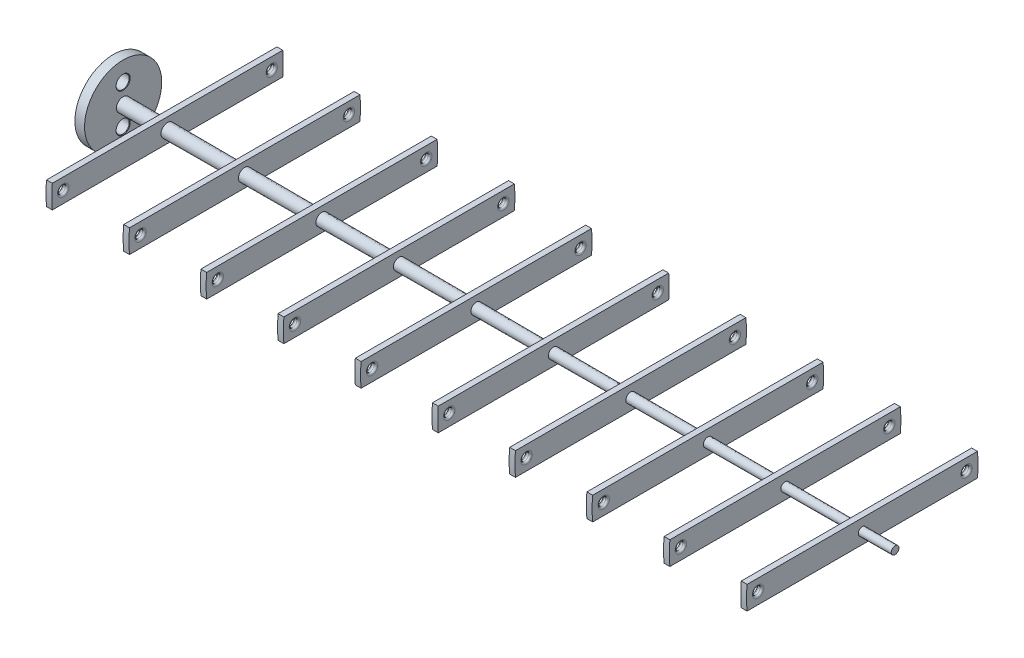
SolidWorks part; units mm, degrees
ref_plane "Front Plane" through (0, 0, 0) normal (0, 0, 1) x (1, 0, 0)
ref_plane "Top Plane" through (0, 0, 0) normal (0, 1, 0) x (1, 0, 0)
ref_plane "Right Plane" through (0, 0, 0) normal (1, 0, 0) x (0, 0, -1)
sketch "Sketch2" plane through (0, 0, 0) normal (0, 0, 1) x (1, 0, 0)
  line L0 (0, 1.75) -> (200, 1)
  line L1 (0, -11) -> (0, 11) construction
  line L2 (200, 1) -> (200, 0)
  line L3 (200, 0) -> (0, 0)
  line L4 (0, 0) -> (0, 1.75)
  dimension "D1" = 1.75
  dimension "D2" = 200
  dimension "D3" = 1
revolve "Revolve1" add sketch "Sketch2" angle 360 about L3
ref_axis "Axis1" through (-3.9062, 0, 0) along (1, 0, 0)
sketch "Sketch3" plane through (0, 0, 0) normal (0, 0, 1) x (1, 0, 0)
  line L0 (10, 0) -> (10, 30)
  line L1 (10, 30) -> (11.5, 30)
  line L2 (11.5, 30) -> (11.5, 0)
  line L3 (11.5, 0) -> (10, 0)
  line L4 (0, -24.75) -> (0, 24.75) construction
  dimension "D1" = 1.5
  dimension "D2" = 30
  dimension "D3" = 10
revolve "Revolve2" add sketch "Sketch3" angle 360 about L3
sketch "Sketch5" plane through (11.5, 0, 0) normal (1, 0, 0) x (0, 0, -1)
  line L0 (-27, 0) -> (0, 0) construction
  line L1 (0, 0) -> (27, 0) construction
  circle A0 centre (-27, 0) radius 1
  circle A1 centre (27, 0) radius 1
  dimension "D2" = 2
  dimension "D1" = 27
extrude "Cut-Extrude1" cut sketch "Sketch5" against normal up to next
fillet "Fillet1" radius 0.5 4 edges at (10, -1, -27) (10, -1, 27) (11.5, 1, 27) (11.5, 1, -27)
sketch "Sketch24" plane through (11.5, 0, 0) normal (1, 0, 0) x (0, 0, -1)
  line L0 (-29.8492, 3.0039) -> (29.8492, 3.0039)
  line L1 (-29.8496, -3) -> (29.8496, -3)
  circle A0 centre (0, 0) radius 30 construction
  arc A1 (-29.8496, -3) -> (29.8496, -3) centre (0, 0) ccw
  circle M6 centre (0, 0) radius 30
  dimension "D1" = 3.0039
  dimension "D2" = 3
extrude "Cut-Extrude2" cut sketch "Sketch24" against normal through all and the other way through all contours L0 M6 | L1 M6 region at (11.5, 14.3704, 0) region at (11.5, -14.3683, 0)
pattern_linear "LPattern1" count 10 spacing 20 along (1, 0, 0) of "Revolve2", "Cut-Extrude2", "Cut-Extrude1", "Fillet1"
sketch "Sketch16" plane through (0, 0, 0) normal (-1, 0, 0) x (0, 0, 1)
  circle A0 centre (0, 0) radius 10
  dimension "D1" = 20
extrude "Boss-Extrude1" add sketch "Sketch16" along normal blind 2.5
sketch "Sketch19" plane through (0, 0, 0) normal (-1, 0, 0) x (0, 0, 1)
  line L0 (0, 5) -> (0, -5) construction
  line L1 (0, -3.3021) -> (0, 3.3021) construction
  point P7 (0, 0)
  point P9 (0, 5)
  point P11 (0, -5)
  dimension "D1" = 10
sketch "Sketch22" plane through (0, 0, 0) normal (1, 0, 0) x (0, 0, -1)
  point P9 (0, 5)
  point P12 (0, -5)
hole_wizard "M3 Clearance Hole2" positions "Sketch22" profile "Sketch21" hole size "M3" standard "ANSI Metric" end condition up to next
sketch "Sketch21" plane through (0, 5, 0) normal (0, 1, 0) x (0, 0, -1)
  line L0 (0, 0) -> (0, 2.5)
  line L1 (0, 2.5) -> (1.7, 2.5)
  line L2 (1.7, 2.5) -> (1.7, 0.125)
  line L3 (1.7, 0.125) -> (1.825, 0)
  line L5 (1.825, 0) -> (0, 0)
  line L6 (-1.7, 0.125) -> (-1.825, 0) construction
  line L11 (0, -6.35) -> (0, 107.95) construction
  dimension "Thru Hole Dia." = 3.4
  dimension "Thru Hole Depth" = 2.5
  dimension "Near C'Sink Dia." = 3.65
  dimension "Near C'Sink Angle" = 90
equation "\"R_initial\"= 1.75"
equation "\"D1@Sketch2\"=\"R_initial\""
equation "\"R_distal\"= 1"
equation "\"D3@Sketch2\"=\"R_distal\""
equation "\"L\"=200"
equation "\"D2@Sketch2\"=\"L\""
equation "\"disk_thickness\"= 1.5"
equation "\"D1@Sketch3\"=\"disk_thickness\""
equation "\"disk_radius\"= 30"
equation "\"D2@Sketch3\"=\"disk_radius\""
equation "\"disk_spacing_initial\"= 10"
equation "\"D3@Sketch3\"=\"disk_spacing_initial\""
equation "\"tendon_routing_radius\"= 27"
equation "\"D1@Sketch5\"=\"tendon_routing_radius\""
equation "\"tendon_routing_hole_radius\"=2"
equation "\"D2@Sketch5\"=\"tendon_routing_hole_radius\""
equation "\"tendon_routing_hole_fillet\"=0.5"
equation "\"D1@Fillet1\"=\"tendon_routing_hole_fillet\""
equation "\"inter_disk_spacing\"= 20"
equation "\"D3@LPattern1\"=\"inter_disk_spacing\""
equation "\"num_disk\"= 10"
equation "\"D1@LPattern1\"=\"num_disk\""
